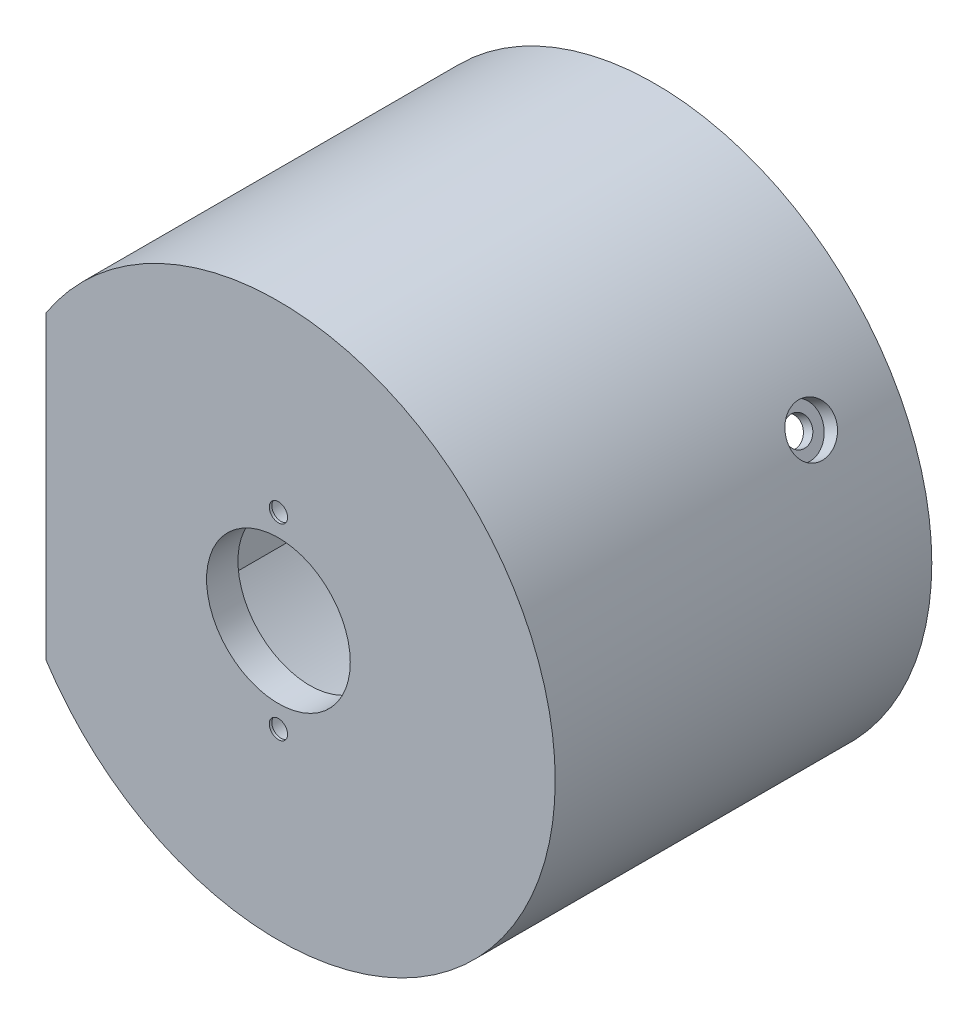
SolidWorks part; units mm, degrees
material "Acrylic (Medium-high impact)"
ref_plane "Front Plane" through (0, 0, 0) normal (0, 0, 1) x (1, 0, 0)
ref_plane "Top Plane" through (0, 0, 0) normal (0, 1, 0) x (1, 0, 0)
ref_plane "Right Plane" through (0, 0, 0) normal (1, 0, 0) x (0, 0, -1)
sketch "Sketch1" plane through (0, 0, 0) normal (0, 0, 1) x (1, 0, 0)
  line L0 (-20.828, 14.4268) -> (-20.828, -14.4268)
  line L1 (-23.495, 15.2375) -> (-23.495, -15.2375)
  arc A0 (-20.828, -14.4268) -> (-20.828, 14.4268) centre (0, 0) ccw
  arc A1 (-23.495, -15.2375) -> (-23.495, 15.2375) centre (0, 0) ccw
  dimension "D1" = 50.673
  dimension "D2" = 2.667
  dimension "D3" = 2.667
  dimension "D4" = 20.828
extrude "Boss-Extrude1" add sketch "Sketch1" along normal blind 39.878
sketch "Sketch10" plane through (0, 0, 39.878) normal (0, 0, 1) x (1, 0, 0)
  line L0 (-23.495, 15.2375) -> (-23.495, -15.2375) construction
  line L1 (-23.495, 15.2375) -> (-23.495, -15.2375)
  arc A0 (-23.495, -15.2375) -> (-23.495, 15.2375) centre (0, 0) ccw
  circle A1 centre (0, 0) radius 28.0035 construction
extrude "Boss-Extrude2" add sketch "Sketch10" against normal blind 3.175
ref_plane "Plane1" through (0, 0, 10.2108) normal (0, 0, -1) x (-1, 0, 0)
sketch "Sketch11" plane through (0, 0, 10.2108) normal (0, 0, -1) x (-1, 0, 0)
  line L0 (0, 0) -> (0, -28.0035) construction
  line L1 (0, 0) -> (-24.2517, 14.0018) construction
  line L2 (0, 0) -> (24.2517, 14.0018) construction
  circle A0 centre (0, 0) radius 28.0035 construction
  dimension "D1" = 120
ref_plane "Plane2" through (-24.2517, 14.0018, 10.2108) normal (-0.866, 0.5, 0) x (0, 0, -1)
ref_plane "Plane3" through (24.2517, 14.0018, 10.2108) normal (0.866, 0.5, 0) x (0, 0, 1)
ref_plane "Plane4" through (0, -28.0035, 10.2108) normal (0, -1, 0) x (-1, 0, 0)
hole_wizard "CBORE for #2 Pan Head Machine Screw1" positions "Sketch15" profile "Sketch14" counterbore size "#2" standard "ANSI Inch" end condition up to next
sketch "Sketch15" plane through (-23.495, 13.799, 10.2108) normal (-1, 0, 0) x (0, 0, -1)
  point P0 (1.6708, 13.799)
sketch "Sketch14" plane through (-23.495, 0, 8.54) normal (0, 1, 0) x (0, 0, 1)
  line L0 (0, 0) -> (0, 2.667)
  line L1 (0, 2.667) -> (1.3525, 2.667)
  line L3 (1.3525, 2.667) -> (1.3525, 1.5748)
  line L4 (1.3525, 1.5748) -> (2.3812, 1.5748)
  line L5 (2.3812, 1.5748) -> (2.3812, 0)
  line L7 (2.3812, 0) -> (0, 0)
  line L11 (0, -6.35) -> (0, 107.95) construction
  dimension "Thru Hole Dia." = 2.7051
  dimension "Thru Hole Depth" = 2.667
  dimension "C'Bore Dia." = 4.7625
  dimension "C'Bore Depth" = 1.5748
hole_wizard "CBORE for #2 Pan Head Machine Screw2" positions "Sketch17" profile "Sketch16" counterbore size "#2" standard "ANSI Inch" end condition up to next
sketch "Sketch17" plane through (24.2517, 14.0018, 10.2108) normal (0.866, 0.5, 0) x (0, 0, 1)
  point P0 (0, 0)
sketch "Sketch16" plane through (24.2517, 14.0018, 10.2108) normal (0, 0, 1) x (-0.5, 0.866, 0)
  line L0 (0, 0) -> (0, 2.667)
  line L1 (0, 2.667) -> (1.3526, 2.667)
  line L3 (1.3526, 2.667) -> (1.3526, 1.5748)
  line L4 (1.3526, 1.5748) -> (2.3812, 1.5748)
  line L5 (2.3812, 1.5748) -> (2.3812, 0)
  line L7 (2.3812, 0) -> (0, 0)
  line L11 (0, -6.35) -> (0, 107.95) construction
  dimension "Thru Hole Dia." = 2.7051
  dimension "Thru Hole Depth" = 2.667
  dimension "C'Bore Dia." = 4.7625
  dimension "C'Bore Depth" = 1.5748
hole_wizard "CBORE for #2 Pan Head Machine Screw3" positions "Sketch19" profile "Sketch18" counterbore size "#2" standard "ANSI Inch" end condition up to next
sketch "Sketch19" plane through (0, -28.0035, 10.2108) normal (0, -1, 0) x (-1, 0, 0)
  point P0 (0, 0)
sketch "Sketch18" plane through (0, -28.0035, 10.2108) normal (1, 0, 0) x (0, 0, -1)
  line L0 (0, 0) -> (0, 2.667)
  line L1 (0, 2.667) -> (1.3526, 2.667)
  line L3 (1.3526, 2.667) -> (1.3526, 1.5748)
  line L4 (1.3526, 1.5748) -> (2.3812, 1.5748)
  line L5 (2.3812, 1.5748) -> (2.3812, 0)
  line L7 (2.3812, 0) -> (0, 0)
  line L11 (0, -6.35) -> (0, 107.95) construction
  dimension "Thru Hole Dia." = 2.7051
  dimension "Thru Hole Depth" = 2.667
  dimension "C'Bore Dia." = 4.7625
  dimension "C'Bore Depth" = 1.5748
sketch "Sketch20" plane through (0, 0, 39.878) normal (0, 0, 1) x (1, 0, 0)
  circle A0 centre (0, 0) radius 7.27
  circle A1 centre (0, 0) radius 6 construction
  dimension "D1" = 1.27
extrude "Cut-Extrude1" cut sketch "Sketch20" against normal up to next
hole_wizard "Hole1" positions "Sketch21" profile "Sketch22" legacy
sketch "Sketch21" plane through (0, 0, 36.703) normal (0, 0, -1) x (-1, 0, 0)
  point P0 (0, 9.5)
  point P3 (0, -9.5)
sketch "Sketch22" plane through (0, 9.5, 36.703) normal (1, 0, 0) x (0, 1, 0)
  line L0 (0, 0) -> (0, 2.921)
  line L1 (0, 2.921) -> (1.4986, 2.921)
  line L2 (1.4986, 2.921) -> (1.6383, 0)
  line L3 (1.6383, 0) -> (0, 0)
  line L4 (0, 110) -> (0, -10) construction
  dimension "Minor Diameter" = 2.9972
  dimension "Depth" = 2.921
  dimension "Major Diameter" = 3.2766
hole_wizard "#0 Clearance Hole1" positions "Sketch23" profile "Sketch24" hole size "#0" standard "ANSI Inch" end condition up to next
sketch "Sketch23" plane through (0, 0, 36.703) normal (0, 0, -1) x (-1, 0, 0)
  point P0 (0, 9.5)
  point P3 (0, -9.5)
sketch "Sketch24" plane through (0, 9.5, 36.703) normal (1, 0, 0) x (0, 1, 0)
  line L0 (0, 0) -> (0, 3.175)
  line L1 (0, 3.175) -> (0.9271, 3.175)
  line L2 (0.9271, 3.175) -> (0.9271, 0)
  line L5 (0.9271, 0) -> (0, 0)
  line L11 (0, -6.35) -> (0, 107.95) construction
  dimension "Thru Hole Dia." = 1.8542
  dimension "Thru Hole Depth" = 3.175
sketch "Sketch25" plane through (0, 0, 0) normal (0, 0, -1) x (-1, 0, 0)
  line L1 (23.495, -15.2375) -> (23.495, 15.2375)
  line L2 (23.495, -15.2375) -> (23.495, 15.2375)
  line L3 (20.828, -14.4268) -> (20.828, 14.4268)
  line L4 (20.828, -14.4268) -> (20.828, 14.4268)
  arc A1 (23.495, 15.2375) -> (23.495, -15.2375) centre (0, 0) ccw
  arc A2 (23.495, 15.2375) -> (23.495, -15.2375) centre (0, 0) ccw
  arc A3 (20.828, 14.4268) -> (20.828, -14.4268) centre (0, 0) ccw
  arc A4 (20.828, 14.4268) -> (20.828, -14.4268) centre (0, 0) ccw
  dimension "D1" = 0
  dimension "D2" = 0
extrude "Cut-Extrude2" cut sketch "Sketch25" against normal blind 1.778
chamfer "Chamfer1" distance 1.27 angle 45 2 edges at (25.3365, 0, 1.778) (-20.828, 0, 1.778)
equation "\"D3@Sketch1\"=\"D2@Sketch1\""
